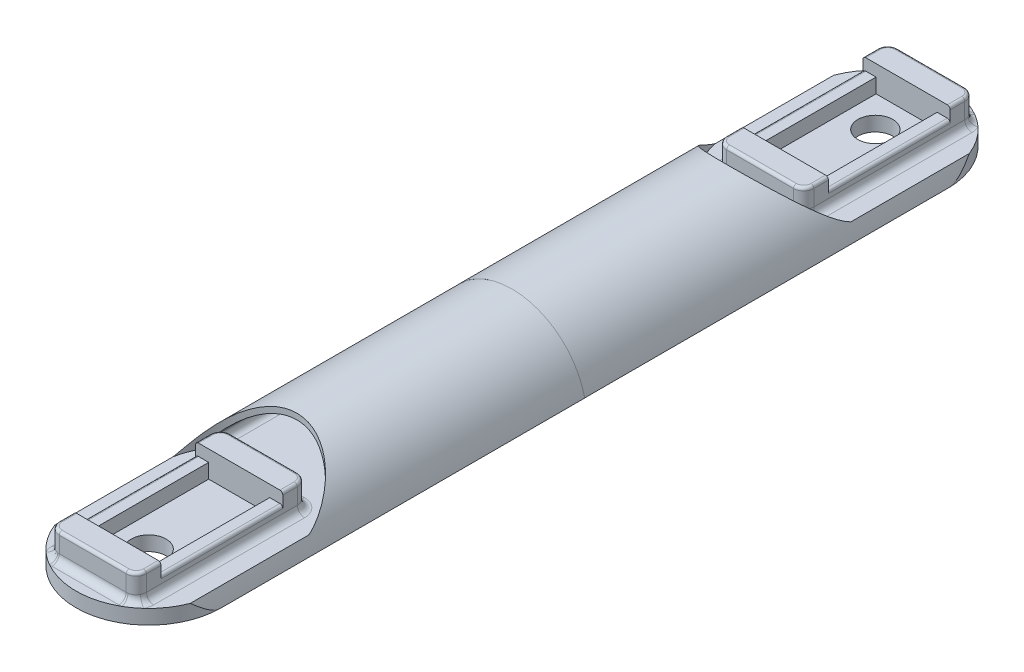
SolidWorks part; units mm, degrees
material "pla filament"
ref_plane "Ön Düzlem" through (0, 0, 0) normal (0, 0, 1) x (1, 0, 0)
ref_plane "Üst Düzlem" through (0, 0, 0) normal (0, 1, 0) x (1, 0, 0)
ref_plane "Sağ Düzlem" through (0, 0, 0) normal (1, 0, 0) x (0, 0, -1)
sketch "Sketch2" plane through (0, 0, 0) normal (0, 0, 1) x (1, 0, 0)
  line L0 (2.6393, 2) -> (47.3607, 2)
  line L1 (0, 0) -> (50, 0)
  arc A0 (0, 0) -> (50, 0) centre (25, -5.625) cw
  arc A1 (2.6393, 2) -> (47.3607, 2) centre (25, -5.625) cw
  dimension "D1" = 25.625
  dimension "D2" = 2
extrude "Boss-Extrude1" add sketch "Sketch2" along normal blind 300
sketch "Sketch3" plane through (0, 0, 300) normal (0, 0, 1) x (1, 0, 0)
  line L0 (0, 0) -> (50, 0) construction
  line L1 (2.2033, 0) -> (47.9135, 0)
  line L2 (2.2033, 0) -> (2.2033, 5)
  line L3 (7.443, 5) -> (42.557, 5)
  line L4 (47.9135, 0) -> (47.9135, 5)
  line L5 (2.6393, 2) -> (47.3607, 2) construction
  line L6 (2.6393, 2) -> (47.3607, 2)
  arc A0 (47.3607, 2) -> (2.6393, 2) centre (25, -5.625) ccw construction
  arc A2 (44.1808, 8.1676) -> (42.557, 5) centre (42.557, 7) cw
  arc A3 (7.443, 5) -> (5.8192, 8.1676) centre (7.443, 7) cw
  arc A4 (47.3607, 2) -> (44.1808, 8.1676) centre (25, -5.625) ccw
  arc A5 (5.8192, 8.1676) -> (2.6393, 2) centre (25, -5.625) ccw
  dimension "D2" = 2
  dimension "D1" = 5
extrude "Boss-Extrude2" add sketch "Sketch3" against normal blind 300 contours L3 A2 A4 L6 A5 A3
sketch "Sketch4" plane through (0, 0, 0) normal (0, -1, 0) x (1, 0, 0)
  line L1 (0, 275) -> (50, 275)
  line L3 (0, 275) -> (50, 275)
  line L4 (0, 275) -> (0, 300)
  line L5 (0, 300) -> (50, 300)
  line L6 (50, 275) -> (50, 300)
  line L7 (50, 300) -> (50, 0) construction
  line L8 (0, 0) -> (50, 0)
  line L9 (0, 0) -> (0, 25)
  line L10 (0, 25) -> (50, 25)
  line L11 (50, 0) -> (50, 25)
  arc A1 (50, 275) -> (0, 275) centre (25, 275) ccw
  arc A3 (0, 25) -> (50, 25) centre (25, 25) ccw
  line M10 (0, 0) -> (50, 0)
  line M11 (50, 0) -> (50, 300)
  line M12 (50, 300) -> (0, 300)
  line M13 (0, 300) -> (0, 0)
  dimension "D1" = 25
extrude "Cut-Extrude2" cut sketch "Sketch4" against normal blind 200 contours A1 M11 M12 | A1 L5 M13 | A3 M13 M10 | A3 L8 M11 region at (5.5842, 0, 294.4158) region at (44.4158, 0, 294.4158) region at (5.5842, 0, 5.5842) region at (44.4158, 0, 5.5842)
sketch "Sketch5" plane through (0, 5, 0) normal (0, 1, 0) x (1, 0, 0)
  line L0 (1.25, -25) -> (1.25, -13.5745)
  line L1 (1.25, -13.5745) -> (14.1618, 8.5504)
  line L2 (14.1618, 8.5504) -> (43.6578, 1.4949)
  line L3 (43.6578, 1.4949) -> (48.75, -2.3752)
  line L4 (48.75, -25) -> (48.75, -2.3752)
  line L5 (0, -150) -> (126.4795, -150) construction
  line L6 (0, -275) -> (0, -25) construction
  line L7 (48.75, -275) -> (48.75, -251.25)
  line L8 (1.25, -275) -> (1.25, -251.25)
  line L9 (48.75, -275) -> (48.75, -297.6248)
  line L10 (43.6578, -301.4949) -> (48.75, -297.6248)
  line L11 (14.1618, -308.5504) -> (43.6578, -301.4949)
  line L12 (1.25, -286.4255) -> (14.1618, -308.5504)
  line L14 (1.25, -25) -> (1.25, -48.75)
  line L16 (48.75, -25) -> (48.75, -48.75)
  line L17 (1.25, -275) -> (1.25, -286.4255)
  line L18 (1.25, -251.25) -> (1.25, -247.75)
  line L19 (48.75, -48.75) -> (48.75, -52.25)
  line L20 (48.75, -251.25) -> (48.75, -247.75)
  line L21 (1.25, -48.75) -> (1.25, -52.25)
  line L22 (1.25, -25) -> (1.25, -13.5745)
  line L23 (1.25, -13.5745) -> (14.1618, 8.5504)
  line L24 (14.1618, 8.5504) -> (43.6578, 1.4949)
  line L25 (43.6578, 1.4949) -> (48.75, -2.3752)
  line L26 (48.75, -25) -> (48.75, -2.3752)
  line L27 (1.25, -25) -> (1.25, -48.75)
  line L28 (48.75, -25) -> (48.75, -48.75)
  arc A5 (1.25, -247.75) -> (48.75, -247.75) centre (25, -247.75) cw
  arc A6 (1.25, -52.25) -> (48.75, -52.25) centre (25, -52.25) ccw
  line M2 (7.443, -7.2025) -> (7.443, -292.7975)
  arc M3 (7.443, -292.7975) -> (42.557, -292.7975) centre (25, -275) ccw
  line M4 (42.557, -292.7975) -> (42.557, -7.2025)
  arc M20 (42.557, -7.2025) -> (7.443, -7.2025) centre (25, -25) ccw
extrude "Cut-Extrude9" cut sketch "Sketch5" along normal blind 200 contours M2 M4 M20 | L0 L4 L3 L2 L1 M2 M20 M4 | M4 M2 M3 | L12 L11 L10 M4 M3 M2 region at (2.153, 5, 19.2873) region at (25, 5, 37.9316) region at (6.54, 5, 262.2767) region at (25, 5, 262.0684)
sketch "Sketch6" plane through (0, 5, 0) normal (0, 1, 0) x (1, 0, 0)
  circle A0 centre (25, -25) radius 6
  circle A1 centre (25, -275) radius 6
  arc A2 (48.3184, -15.9861) -> (1.6816, -15.9861) centre (25, -25) ccw construction
  arc A3 (1.6816, -284.0139) -> (48.3184, -284.0139) centre (25, -275) ccw construction
  point P6 (25, 0)
  point P14 (25, -300)
  dimension "D1" = 12
  dimension "D2" = 25
  dimension "D3" = 12
extrude "Cut-Extrude10" cut sketch "Sketch6" against normal blind 200
sketch "Sketch8" plane through (0, 5, 0) normal (0, 1, 0) x (1, 0, 0)
  line L3 (9.9858, -243.8434) -> (39.9858, -243.8434)
  line L4 (9.9858, -243.8434) -> (9.9858, -238.8434)
  line L5 (13.4858, -235.3434) -> (36.4858, -235.3434)
  line L6 (39.9858, -243.8434) -> (39.9858, -238.8434)
  line L7 (13.4858, -294.2434) -> (36.4858, -294.2434)
  line L8 (39.9858, -285.7434) -> (39.9858, -290.7434)
  line L9 (9.9858, -285.7434) -> (39.9858, -285.7434)
  line L10 (9.9858, -285.7434) -> (9.9858, -290.7434)
  line L12 (35.4858, -235.3434) -> (36.4858, -235.3434)
  line L13 (35.4858, -243.8434) -> (35.4858, -285.7434)
  line L14 (35.4858, -294.2434) -> (36.4858, -294.2434)
  line L15 (39.9858, -238.8434) -> (39.9858, -290.7434)
  line L16 (13.4858, -294.2434) -> (14.4858, -294.2434)
  line L17 (9.9858, -290.7434) -> (9.9858, -238.8434)
  line L18 (13.4858, -235.3434) -> (14.4858, -235.3434)
  line L19 (14.4858, -285.7434) -> (14.4858, -243.8434)
  arc A0 (13.4858, -294.2434) -> (9.9858, -290.7434) centre (13.4858, -290.7434) cw
  arc A1 (36.4858, -294.2434) -> (39.9858, -290.7434) centre (36.4858, -290.7434) ccw
  arc A2 (9.9858, -238.8434) -> (13.4858, -235.3434) centre (13.4858, -238.8434) cw
  arc A3 (36.4858, -235.3434) -> (39.9858, -238.8434) centre (36.4858, -238.8434) cw
  dimension "D1" = 3.5
extrude "Boss-Extrude3" add sketch "Sketch8" along normal blind 9 contours A3 L5 A2 L4 L3 L6 | L7 A1 L8 L9 L10 A0 region at (24.9858, 5, 239.6664) region at (24.9858, 5, 289.9204)
sketch "Sketch9" plane through (0, 5, 0) normal (0, 1, 0) x (1, 0, 0)
  line L0 (14.4858, -285.7434) -> (14.4858, -243.8434) construction
  line L1 (35.4858, -243.8434) -> (35.4858, -285.7434) construction
  line L2 (39.9858, -285.7434) -> (39.9858, -290.7434) construction
  line L3 (9.9858, -285.7434) -> (39.9858, -285.7434) construction
  line L4 (9.9858, -285.7434) -> (9.9858, -290.7434) construction
  line L5 (9.9858, -290.7434) -> (9.9858, -238.8434) construction
  line L6 (39.9858, -238.8434) -> (39.9858, -290.7434) construction
  line L7 (13.4858, -294.2434) -> (36.4858, -294.2434) construction
  line L8 (35.4858, -294.2434) -> (36.4858, -294.2434) construction
  line L9 (13.4858, -294.2434) -> (14.4858, -294.2434) construction
  line L10 (13.4858, -235.3434) -> (14.4858, -235.3434) construction
  line L11 (35.4858, -235.3434) -> (36.4858, -235.3434) construction
  line L12 (39.9858, -243.8434) -> (39.9858, -238.8434) construction
  line L13 (9.9858, -243.8434) -> (39.9858, -243.8434) construction
  line L14 (9.9858, -243.8434) -> (9.9858, -238.8434) construction
  line L15 (13.4858, -235.3434) -> (36.4858, -235.3434) construction
  line L16 (14.4858, -285.7434) -> (14.4858, -243.8434)
  line L17 (35.4858, -243.8434) -> (35.4858, -285.7434)
  line L18 (39.9858, -285.7434) -> (39.9858, -290.7434)
  line L19 (9.9858, -285.7434) -> (39.9858, -285.7434)
  line L20 (9.9858, -285.7434) -> (9.9858, -290.7434)
  line L21 (9.9858, -290.7434) -> (9.9858, -238.8434)
  line L22 (39.9858, -238.8434) -> (39.9858, -290.7434)
  line L23 (13.4858, -294.2434) -> (36.4858, -294.2434)
  line L24 (35.4858, -294.2434) -> (36.4858, -294.2434)
  line L25 (13.4858, -294.2434) -> (14.4858, -294.2434)
  line L26 (13.4858, -235.3434) -> (14.4858, -235.3434)
  line L27 (35.4858, -235.3434) -> (36.4858, -235.3434)
  line L28 (39.9858, -243.8434) -> (39.9858, -238.8434)
  line L29 (9.9858, -243.8434) -> (39.9858, -243.8434)
  line L30 (9.9858, -243.8434) -> (9.9858, -238.8434)
  line L31 (13.4858, -235.3434) -> (36.4858, -235.3434)
  arc A0 (9.9858, -290.7434) -> (13.4858, -294.2434) centre (13.4858, -290.7434) ccw construction
  arc A1 (36.4858, -294.2434) -> (39.9858, -290.7434) centre (36.4858, -290.7434) ccw construction
  arc A2 (39.9858, -238.8434) -> (36.4858, -235.3434) centre (36.4858, -238.8434) ccw construction
  arc A3 (13.4858, -235.3434) -> (9.9858, -238.8434) centre (13.4858, -238.8434) ccw construction
  arc A4 (9.9858, -290.7434) -> (13.4858, -294.2434) centre (13.4858, -290.7434) ccw
  arc A5 (36.4858, -294.2434) -> (39.9858, -290.7434) centre (36.4858, -290.7434) ccw
  arc A6 (39.9858, -238.8434) -> (36.4858, -235.3434) centre (36.4858, -238.8434) ccw
  arc A7 (13.4858, -235.3434) -> (9.9858, -238.8434) centre (13.4858, -238.8434) ccw
  line M18 (39.9858, -243.8434) -> (9.9858, -243.8434)
  line M24 (9.9858, -285.7434) -> (39.9858, -285.7434)
extrude "Boss-Extrude4" add sketch "Sketch9" along normal blind 5 contours L22 L17 M18 M24 | L21 L16 M24 M18 region at (12.2358, 5, 264.7934) region at (37.7358, 5, 264.7934)
fillet "Fillet1" radius 2.5 8 edges at (11.0109, 5, 293.2183) (24.9858, 5, 294.2434) (38.9607, 5, 293.2183) (39.9858, 5, 264.7934) (38.9607, 5, 236.3685) (24.9858, 5, 235.3434) (11.0109, 5, 236.3685) (9.9858, 5, 264.7934)
fillet "Fillet2" radius 1 10 edges at (9.9858, 14, 241.3434) (11.0109, 14, 236.3685) (39.9858, 14, 241.3434) (38.9607, 14, 236.3685) (24.9858, 14, 235.3434) (9.9858, 14, 288.2434) (11.0109, 14, 293.2183) (39.9858, 14, 288.2434) (38.9607, 14, 293.2183) (24.9858, 14, 294.2434)
fillet "Fillet3" radius 1 2 edges at (9.9858, 10, 264.7934) (39.9858, 10, 264.7934)
sketch "Sketch10" plane through (0, 0, 0) normal (0, 1, 0) x (1, 0, 0)
  line L0 (50, -150) -> (72.8317, -150) construction
  line L1 (50, -275) -> (50, -25) construction
  line L3 (72.8317, -150) -> (-22.6297, -150)
  line L4 (72.8317, -150) -> (72.8317, 9.6279)
  line L5 (72.8317, 9.6279) -> (-22.6297, 9.6279)
  line L6 (-22.6297, -150) -> (-22.6297, 9.6279)
extrude "Cut-Extrude11" cut sketch "Sketch10" along normal through all
ref_plane "Plane1" through (0, 0, 150) normal (0, 0, -1) x (-1, 0, 0)
ref_plane "Plane2" through (24.9858, 0, 0) normal (1, 0, 0) x (0, 0, -1)
ref_axis "Axis1" through (24.9858, 21, 150) along (0, -1, 0)
pattern_circular "CirPattern1" count 2 over 360 about axis through (24.9858, 21, 150) along (0, -1, 0) of bodies 115
combine bodies "Combine2" operation type add bodies to combine 118 115
